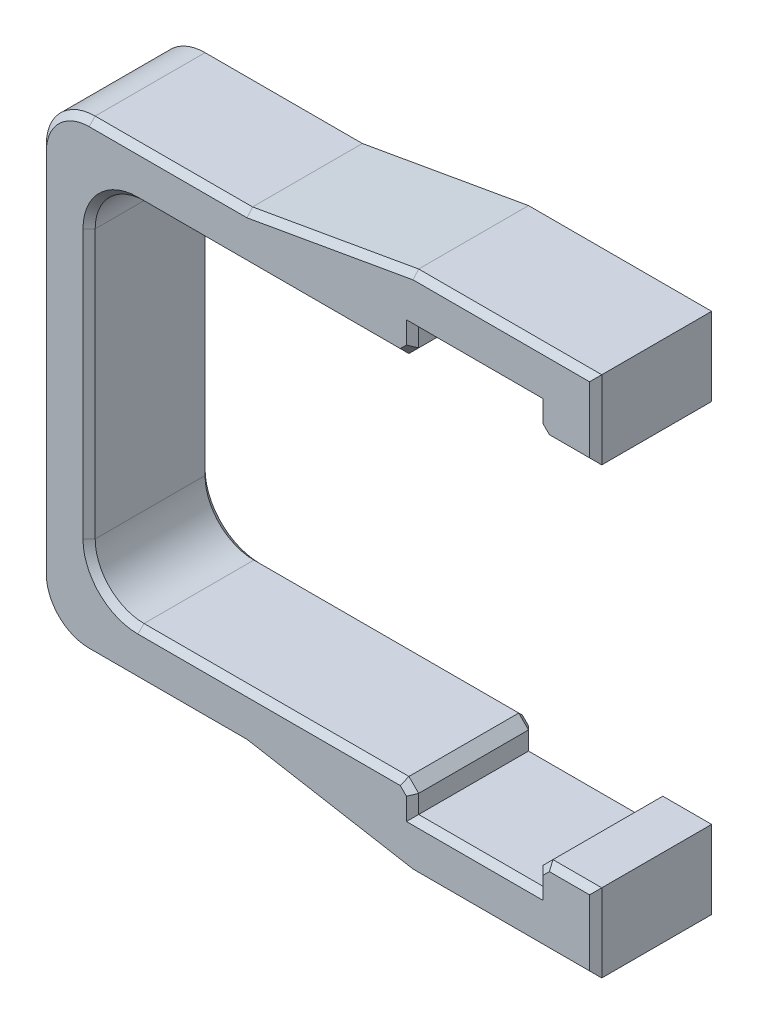
SolidWorks part; units mm, degrees
ref_plane "Top" through (0, 0, 0) normal (0, 0, 1) x (1, 0, 0)
ref_plane "Front" through (0, 0, 0) normal (0, 1, 0) x (1, 0, 0)
ref_plane "Right" through (0, 0, 0) normal (1, 0, 0) x (0, 0, -1)
sketch "Sketch1" plane through (0, 0, 0) normal (0, 0, 1) x (1, 0, 0)
  line L0 (0, 0) -> (0, 38)
  line L1 (0, 38) -> (30.5, 38)
  line L2 (30.5, 38) -> (30.5, 34)
  line L3 (30.5, 34) -> (4, 34)
  line L4 (4, 34) -> (4, 4)
  line L5 (4, 4) -> (30.5, 4)
  line L6 (30.5, 4) -> (30.5, 0)
  line L7 (30.5, 0) -> (0, 0)
  dimension "D1" = 30
  dimension "D2" = 26.5
  dimension "D3" = 4
  dimension "D4" = 4
  dimension "D5" = 4
extrude "Boss-Extrude1" add sketch "Sketch1" along normal blind 10
fillet "Fillet1" radius 4 4 edges at (4, 4, 5) (4, 34, 5) (0, 38, 5) (0, 0, 5)
ref_plane "Plane1" through (30.5, 38, 0) normal (0, 0, -1) x (-1, 0, 0)
sketch "Sketch3" plane through (30.5, 0, 0) normal (1, 0, 0) x (0, 0, -1)
  line L1 (-10, 34) -> (0, 34)
  line L2 (-10, 34) -> (-10, 40.4)
  line L3 (-10, 40.4) -> (0, 40.4)
  line L4 (0, 34) -> (0, 40.4)
  line L7 (0, 4) -> (-10, 4)
  line L8 (0, 4) -> (0, -2.4)
  line L9 (0, -2.4) -> (-10, -2.4)
  line L10 (-10, 4) -> (-10, -2.4)
  dimension "D1" = 6.4
  dimension "D2" = 6.4
extrude "Boss-Extrude2" add sketch "Sketch3" along normal blind 15
sketch "Sketch5" plane through (0, 0, 10) normal (0, 0, 1) x (1, 0, 0)
  line L0 (8, 34) -> (45.5, 34) construction
  line L1 (30.5, 36.3) -> (40.7, 36.3)
  line L2 (30.5, 36.3) -> (30.5, 1.7)
  line L3 (30.5, 1.7) -> (40.7, 1.7)
  line L4 (40.7, 36.3) -> (40.7, 1.7)
  line L5 (45.5, 4) -> (8, 4) construction
  line L6 (30.5, 40.4) -> (30.5, 38) construction
  dimension "D1" = 10.2
  dimension "D2" = 2.3
  dimension "D3" = 2.3
extrude "Cut-Extrude1" cut sketch "Sketch5" against normal blind 15
chamfer "Chamfer2" distance 2.4 angle 80 2 edges at (30.5, 0, 5) (30.5, 38, 5)
chamfer "Chamfer3" distance 0.8 angle 45 4 edges at (40.7, 4, 5) (30.5, 4, 5) (40.7, 34, 5) (30.5, 34, 5)
chamfer "Chamfer1" distance 0.5 angle 45 56 edges at (18.85, 34, 10) (18.85, 34, 0) (5.1716, 32.8284, 10) (5.1716, 32.8284, 0) (4, 19, 10) (4, 19, 0) (5.1716, 5.1716, 10) (5.1716, 5.1716, 0) (18.85, 4, 10) (18.85, 4, 0) (10.4445, 0, 0) (10.4445, 0, 10) (1.1716, 1.1716, 10) (1.1716, 1.1716, 0) (0, 19, 10) (0, 19, 0) (1.1716, 36.8284, 10) (1.1716, 36.8284, 0) (10.4445, 38, 10) (10.4445, 38, 0) (45.5, 0.8, 10) (38, -2.4, 10) (23.6945, -1.2, 10) (23.6945, -1.2, 0) (23.6945, 39.2, 10) (23.6945, 39.2, 0) (38, 40.4, 10) (45.5, 37.2, 10) (43.5, 34, 10) (43.5, 34, 0) (41.1, 34.4, 10) (41.1, 34.4, 0) (40.7, 35.55, 0) (40.7, 35.55, 10) (35.6, 36.3, 0) (35.6, 36.3, 10) (30.5, 35.55, 10) (30.5, 35.55, 0) (30.1, 34.4, 0) (30.1, 34.4, 10) (30.1, 3.6, 10) (30.1, 3.6, 0) (30.5, 2.45, 0) (30.5, 2.45, 10) (35.6, 1.7, 0) (35.6, 1.7, 10) (40.7, 2.45, 10) (40.7, 2.45, 0) (41.1, 3.6, 0) (41.1, 3.6, 10) (43.5, 4, 10) (43.5, 4, 0) (45.5, 37.2, 0) (38, 40.4, 0) (38, -2.4, 0) (45.5, 0.8, 0)
